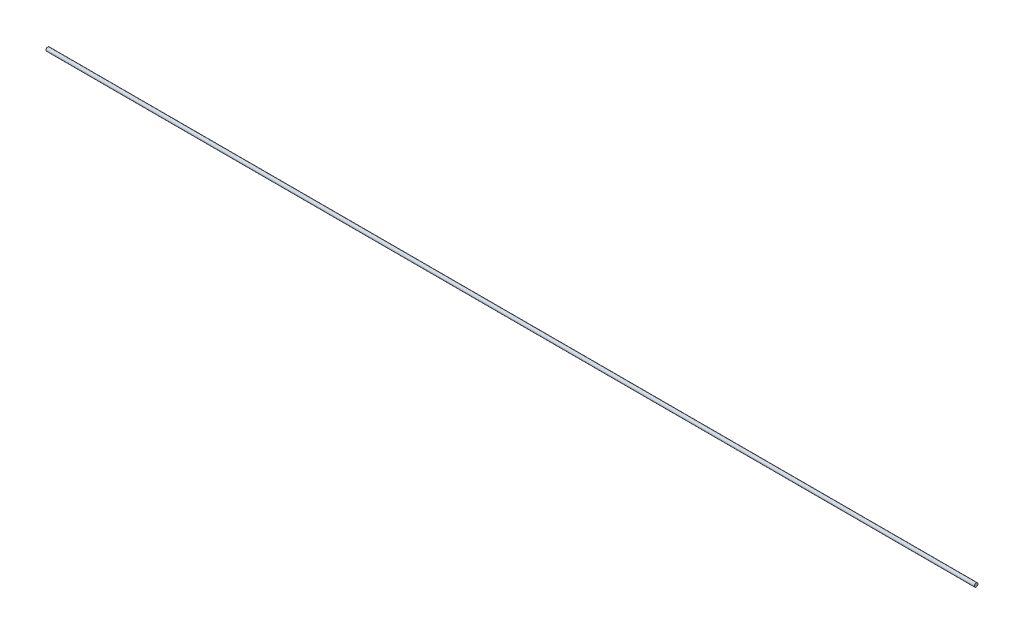
SolidWorks part; units mm, degrees
ref_plane "Front Plane" through (0, 0, 0) normal (0, 0, 1) x (1, 0, 0)
ref_plane "Top Plane" through (0, 0, 0) normal (0, 1, 0) x (1, 0, 0)
ref_plane "Right Plane" through (0, 0, 0) normal (1, 0, 0) x (0, 0, -1)
sketch "Sketch1" plane through (0, 0, 0) normal (1, 0, 0) x (0, 0, -1)
  line L0 (0.8001, -12.7) -> (0.7937, 0) construction
  line L1 (1.4351, -12.7) -> (1.4351, 0) construction
  line L2 (0.8001, -12.7) -> (1.4351, -12.7) construction
  line L4 (0, 12.7) -> (0, -12.7) construction
  line L5 (0, 0) -> (0.6065, -1.3006) construction
  line L6 (0, 0) -> (0.6065, 1.3006) construction
  circle A0 centre (0, 0) radius 0.7937 construction
  circle A1 centre (0, 0) radius 1.4351 construction
  point P11 (0, 0)
  dimension "Pin Diameter" = 1.5875
  dimension "Knuckle Diameter" = 2.8702
  dimension "Overall Width" = 25.4
  dimension "Leaf Thickness" = 0.635
  dimension "D1" = 25
  dimension "D2" = 25
sketch "Sketch2" plane through (0, 0, 0) normal (0, 0, 1) x (1, 0, 0)
  line L0 (-300.4, 0) -> (300.4, 0) construction
  line L1 (300.4, -12.7) -> (300.4, 12.7)
  line L2 (275, -7.9375) -> (275, 7.9375) construction
  line L3 (272.6378, -7.9375) -> (277.3622, -7.9375) construction
  line L4 (272.6378, 7.9375) -> (277.3622, 7.9375) construction
  point P3 (0, 0)
  point P7 (275, 0)
  point P10 (275, -7.9375)
  point P12 (275, 7.9375)
  point P13 (294.05, 0)
  point P14 (-262.3, 0)
  point P15 (211.5, 0)
  point P16 (-211.5, 0)
  point P20 (300.4, 0)
  dimension "Length" = 600.8
  dimension "Mounting Hole Diameter" = 4.7244
  dimension "End to Mounting Hole" = 25.4
  dimension "Knuckle Length" = 6.35
  dimension "D1" = 38.1
  dimension "D2" = 88.9
  dimension "D3" = 88.9
  dimension "D4" = 25.4
  dimension "Mounting Hole Offset" = 4.7625
sketch "Sketch5" plane through (0, 0, 0) normal (1, 0, 0) x (0, 0, -1)
  line L0 (0, 12.7) -> (0, -12.7) construction
  line L1 (0.6065, -1.3006) -> (0.3381, -0.7251)
  line L2 (0.8001, 0) -> (0.8001, -12.7)
  line L3 (0.8001, -12.7) -> (1.4351, -12.7)
  line L4 (1.4351, -12.7) -> (1.4351, 0)
  line L5 (0, 0) -> (1.4351, 0) construction
  circle A0 centre (0, 0) radius 0.8001 construction
  circle A1 centre (0, 0) radius 1.4351 construction
  arc A2 (0.3381, -0.7251) -> (0.8001, 0) centre (0, 0) cw
  arc A3 (0.6065, -1.3006) -> (1.4351, 0) centre (0, 0) cw
extrude "Boss-Extrude2" [suppressed] add sketch "Sketch5" along normal mid plane 600.8
sketch "Sketch6" [suppressed] plane through (0, 0, 0) normal (0, 0, 1) x (1, 0, 0)
  line L0 (300.4, -1.4351) -> (300.4, 1.4351)
  line L1 (300.4, 1.4351) -> (294.05, 1.4351)
  line L2 (294.05, 1.4351) -> (294.05, -1.4351)
  line L3 (294.05, -1.4351) -> (300.4, -1.4351)
  point P4 (300.4, 0)
  dimension "D1" = 2.8702
  dimension "D2" = 6.35
extrude "Cut-Extrude1" [suppressed] cut sketch "Sketch6" against normal through all both and the other way through all
pattern_linear "LPattern1" [suppressed] count 47 spacing 12.7 of bodies 106
sketch "Sketch7" plane through (0, 0, 0) normal (1, 0, 0) x (0, 0, -1)
  line L0 (-1.4351, 0) -> (1.4351, 0) construction
  point P3 (0, 0)
sketch "Sketch8" [suppressed] plane through (0, 0, -1.4351) normal (0, 0, 1) x (1, 0, 0)
  circle A0 centre (275, -7.9375) radius 2.3622
extrude "Cut-Extrude2" [suppressed] cut sketch "Sketch8" along normal blind 0.635 draft 41 and the other way through all from offset 0.2381 draft outward yes
pattern_linear "LPattern2" [suppressed] count 12 spacing 50.8 of bodies 108
pattern_circular "CirPattern1" [suppressed] count 2 over 360 about axis through (0, 0, 1.4351) along (0, 0, -1) reverse direction yes of bodies 109
sketch "Sketch9" [suppressed] plane through (0, 0, -1.4351) normal (0, 0, -1) x (-1, 0, 0)
  line L0 (300.4, 0) -> (-300.4, 0) construction
  circle A0 centre (-296.2725, 0) radius 0.4784
  dimension "D2" = 0.9567
  dimension "D1" = 2.2225
extrude "Cut-Extrude3" [suppressed] cut sketch "Sketch9" against normal up to next
pattern_linear "LPattern3" [suppressed] count 47 spacing 12.7 of bodies 111
sketch "Sketch10" plane through (0, 0, 0) normal (1, 0, 0) x (0, 0, -1)
  circle A0 centre (0, 0) radius 0.7937
  dimension "D1" = 1.5875
extrude "Boss-Extrude3" add sketch "Sketch10" along normal mid plane 600.8 separate body
chamfer "Chamfer1" distance 0.1588 angle 45 2 edges at (-300.4, 0, -0.7937) (300.4, 0, -0.7937)
sketch "Sketch11" [suppressed] plane through (0, 0, 0) normal (0, 0, 1) x (1, 0, 0)
  line L0 (300.4, 12.7) -> (-300.4, 12.7) construction
  line L1 (275, 7.9375) -> (224.2, 7.9375) construction
  line L2 (300.4, -1.4351) -> (300.4, 1.4351) construction
  line L4 (300.4, 12.7) -> (300.4, -12.7) construction
  line L5 (294.05, -1.4351) -> (294.05, 1.4351) construction
  point P3 (0, 12.7)
  point P4 (-300.4, 12.7)
  point P5 (300.4, 12.7)
  point P10 (275, -7.9375)
  point P11 (224.2, 7.9375)
  point P12 (275, 7.9375)
  point P18 (300.4, 0)
  point P19 (300.4, -1.4351)
  point P21 (300.4, 1.4351)
  point P24 (300.4, 0)
  point P25 (300.4, -12.7)
  point P29 (294.05, 0)
  point P30 (294.05, -1.4351)
  point P32 (294.05, 1.4351)
  dimension "D1" = 600.8
  dimension "D2" = 2.8702
  dimension "D4" = 50.8
sketch "Sketch12" plane through (0, 0, 0) normal (1, 0, 0) x (0, 0, -1)
  line L0 (1.4351, -12.7) -> (1.4351, 12.7) construction
  line L1 (1.4351, 12.7) -> (0.8001, 12.7) construction
  line L2 (0.8001, 12.7) -> (0.8001, -12.7) construction
  line L3 (0.8001, -12.7) -> (1.4351, -12.7) construction
  line L4 (0, -0.7937) -> (0, 0.7937) construction
  line L6 (0, 12.7) -> (0, -12.7) construction
  point P7 (0.8001, 12.7)
  point P8 (1.4351, 12.7)
  point P9 (1.4351, -12.7)
  point P10 (0.8001, -12.7)
  point P15 (0, 0)
  point P16 (0, 0.7937)
  point P20 (0, -0.7937)
  dimension "D1" = 1.5875
sketch "Sketch13" plane through (300.4, 0, 0) normal (1, 0, 0) x (0, 0, -1)
  circle A0 centre (0, 0) radius 1.9817
  dimension "D1" = 3.9634
extrude "Cut-Extrude4" cut sketch "Sketch13" against normal blind 198.12
equation "\"D1@Boss-Extrude2\"=\"Length@sketch2\""
equation "\"D1@Sketch6\"=\"Knuckle Diameter@sketch1\""
equation "\"D2@Sketch6\"=\"Knuckle length@sketch2\""
equation "\"D3@LPattern1\" = \"Knuckle Length@Sketch2\" * 2"
equation "\"D1@LPattern1\" = \"Length@Sketch2\" /  ( \"Knuckle Length@Sketch2\" * 2 ) "
equation "\"D1@LPattern2\"=\"Length@sketch2\"/2"
equation "\"D1@Sketch9\"=\"Knuckle length@sketch2\"*.35"
equation "\"D2@Sketch9\"=\"Knuckle diameter@sketch1\"/3"
equation "\"D3@LPattern3\"=\"Knuckle length@sketch2\"*2"
equation "\"D1@LPattern3\" = \"Length@Sketch2\" /  ( \"Knuckle Length@Sketch2\" * 2 ) "
equation "\"D1@Sketch10\"=\"Pin diameter@sketch1\""
equation "\"D1@Boss-Extrude3\"=\"length@sketch2\""
equation "\"D1@Chamfer1\"=\"Pin diameter@sketch1\"*.1"
equation "\"D1@Sketch11\"=\"Length@sketch2\""
equation "\"D2@Sketch11\"=\"knuckle diameter@sketch1\""
equation "\"D3@Sketch11\" = \"Overall Width@Sketch1\""
equation "\"D1@Sketch12\"=\"Pin diameter@sketch1\""
equation "\"D3@Sketch2\"=\"D2@Sketch2\""
equation "\"D4@Sketch2\"=\"Overall Width@sketch1\""
equation "\"D1@Cut-Extrude2\"=\"Leaf thickness@sketch1\""
equation "\"D19@Cut-Extrude2\"=\"leaf thickness@sketch1\"*.375"
